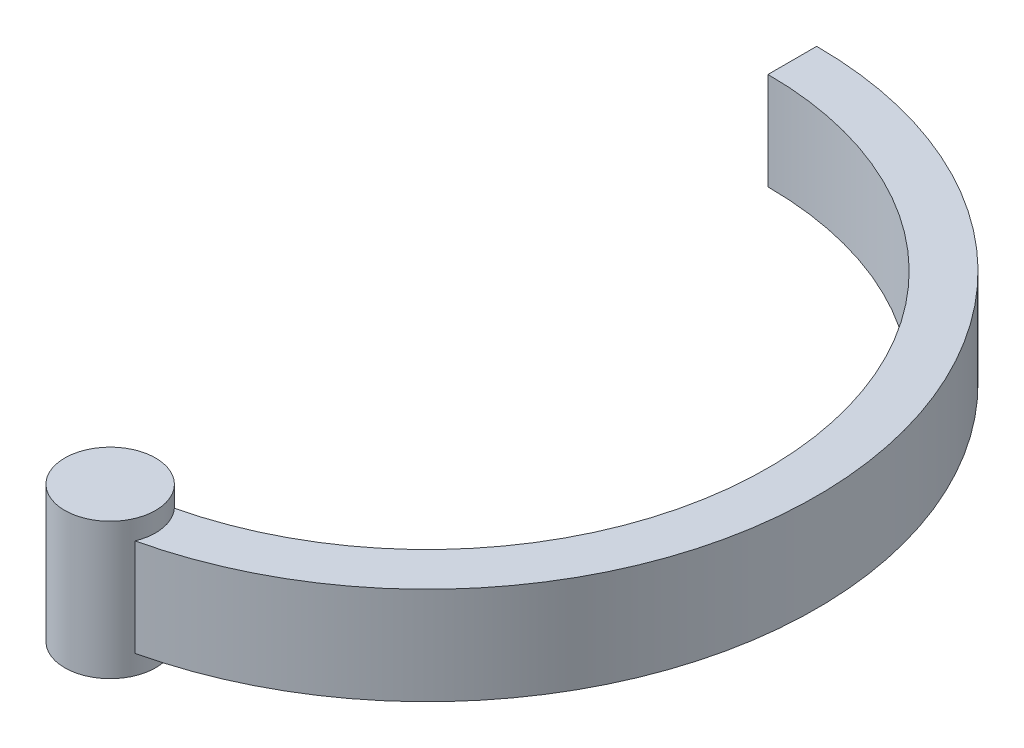
SolidWorks part; units mm, degrees
ref_plane "Спереди" through (0, 0, 0) normal (0, 0, 1) x (1, 0, 0)
ref_plane "Сверху" through (0, 0, 0) normal (0, 1, 0) x (1, 0, 0)
ref_plane "Справа" through (0, 0, 0) normal (1, 0, 0) x (0, 0, -1)
sketch "Эскиз1" plane through (0, 0, 0) normal (0, 1, 0) x (1, 0, 0)
  line L0 (0, 35) -> (0, 40)
  arc A0 (8.0982, -34.0502) -> (0, 35) centre (0, 0) ccw
  arc A1 (8.9813, -38.9787) -> (0, 40) centre (0, 0) ccw
  arc A5 (8.9813, -38.9787) -> (8.0982, -34.0502) centre (4.665, -37.2087) ccw
  dimension "D1" = 70
  dimension "D2" = 5
sketch "Эскиз2" plane through (0, 0, 0) normal (0, 1, 0) x (1, 0, 0)
  circle A0 centre (4.665, -37.2087) radius 4.665
extrude "Бобышка-Вытянуть2" add sketch "Эскиз2" along normal blind 7 and the other way blind 7
extrude "Бобышка-Вытянуть3" add sketch "Эскиз1" along normal blind 5 and the other way blind 5
